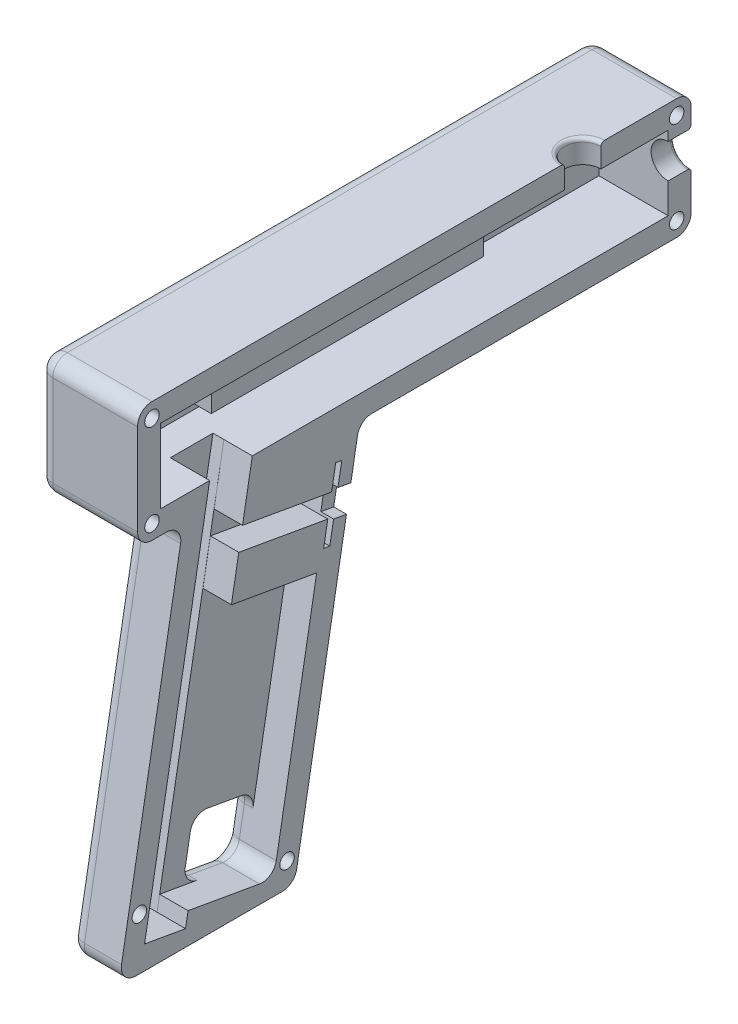
SolidWorks part; units mm, degrees
ref_plane "Front Plane" through (0, 0, 0) normal (0, 0, 1) x (1, 0, 0)
ref_plane "Top Plane" through (0, 0, 0) normal (0, 1, 0) x (1, 0, 0)
ref_plane "Right Plane" through (0, 0, 0) normal (1, 0, 0) x (0, 0, -1)
sketch "Sketch1" plane through (0, 0, 0) normal (0, 0, 1) x (1, 0, 0)
  line L1 (0, 0) -> (27.305, 0)
  line L2 (0, 0) -> (0, 33.1)
  line L3 (0, 33.1) -> (27.305, 33.1)
  line L4 (27.305, 0) -> (27.305, 33.1)
  dimension "D1" = 33.1
  dimension "D2" = 27.305
extrude "Boss-Extrude1" add sketch "Sketch1" against normal blind 152.4
sketch "Sketch2" plane through (27.305, 0, 0) normal (1, 0, 0) x (0, 0, -1)
  line L0 (0, 0) -> (0, 33.1) construction
  line L1 (6.35, 26.75) -> (146.05, 26.75)
  line L2 (6.35, 26.75) -> (6.35, 6.35)
  line L3 (6.35, 6.35) -> (146.05, 6.35)
  line L4 (146.05, 26.75) -> (146.05, 6.35)
  line L5 (152.4, 33.1) -> (0, 33.1) construction
  line L6 (152.4, 0) -> (0, 0) construction
  line L7 (152.4, 0) -> (152.4, 33.1) construction
  point P12 (6.35, 16.55)
  point P13 (0, 16.55)
  dimension "D1" = 6.35
  dimension "D2" = 6.35
  dimension "D3" = 6.35
  dimension "D4" = 6.35
extrude "Cut-Extrude1" cut sketch "Sketch2" against normal blind 19.05
sketch "Sketch4" plane through (0, 33.1, 0) normal (0, 1, 0) x (1, 0, 0)
  line L0 (27.305, 152.4) -> (27.305, 0) construction
  line L2 (27.305, 117.555) -> (27.305, 127.555)
  line L3 (27.305, 152.4) -> (0, 152.4) construction
  arc A2 (27.305, 117.555) -> (27.305, 127.555) centre (27.305, 122.555) cw
  dimension "D1" = 29.845
sketch "Sketch5" plane through (8.255, 0, 0) normal (1, 0, 0) x (0, 0, -1)
  line L0 (33.02, 17.4) -> (107.95, 17.4)
  line L1 (33.02, 23.75) -> (107.95, 23.75)
  line L2 (33.02, 23.75) -> (33.02, 9.35)
  line L3 (33.02, 9.35) -> (107.95, 9.35)
  line L4 (107.95, 23.75) -> (107.95, 9.35)
  line L9 (33.02, 15.7) -> (107.95, 15.7)
  line L10 (6.35, 6.35) -> (146.05, 6.35) construction
  line L11 (146.05, 6.35) -> (146.05, 26.75) construction
  line M13 (146.05, 6.35) -> (146.05, 26.75)
  dimension "D1" = 1.7
  dimension "D2" = 6.35
  dimension "D3" = 6.35
  dimension "D4" = 3
  dimension "D5" = 38.1
  dimension "D6" = 74.93
extrude "PCB Slot" add sketch "Sketch5" along normal blind 6.35 contours L1 L2 L0 M13 | L9 L2 L3 M13 region at (8.255, 20.575, -70.485) region at (8.255, 12.525, -70.485)
sketch "Sketch8" plane through (27.305, 0, 25.4) normal (1, 0, 0) x (0, 0, -1)
  line L0 (38.1, 0) -> (20.1852, -101.6)
  line L1 (20.1852, -101.6) -> (68.621, -101.6)
  line L2 (68.621, -101.6) -> (86.5358, 0)
  line L4 (38.1, 0) -> (86.5358, 0)
  dimension "D1" = 12.7
  dimension "D3" = 47.7
extrude "Butt" add sketch "Sketch8" against normal blind 14.175
sketch "Sketch9" plane through (27.305, 0, 25.4) normal (1, 0, 0) x (0, 0, -1)
  line L7 (68.621, -101.6) -> (86.5358, 0) construction
  line L8 (51.2564, -26.2652) -> (74.7269, -30.4036)
  line L9 (28.0575, -91.2236) -> (62.9188, -97.3706)
  line L10 (74.7269, -30.4036) -> (62.9188, -97.3706)
  line L12 (31.75, 6.35) -> (171.45, 6.35) construction
  line L13 (45.2623, 6.35) -> (57.0073, 6.35)
  line L14 (57.0073, 6.35) -> (51.2564, -26.2652)
  line L15 (45.2623, 6.35) -> (28.0575, -91.2236)
  dimension "D3" = 68
  dimension "D4" = 3.175
extrude "BatteryPack" cut sketch "Sketch9" against normal blind 7.825
sketch "Sketch10" plane through (19.48, 0, 0) normal (1, 0, 0) x (0, 0, -1)
  line L0 (37.5188, -97.3706) -> (20.2847, -94.3317)
  line L1 (37.5188, -97.3706) -> (40.2972, -81.6136)
  line L2 (20.2847, -94.3317) -> (23.0631, -78.5748)
  line L3 (40.2972, -81.6136) -> (23.0631, -78.5748)
  line L4 (2.6575, -91.2236) -> (37.5188, -97.3706) construction
  dimension "D1" = 16
  dimension "D2" = 17.5
extrude "BatterySwitch" cut sketch "Sketch10" against normal up to next
sketch "Sketch11" plane through (0, -88.0184, 15.52) normal (0, 0.9848, -0.1736) x (1, 0, 0)
  line L0 (19.48, 18.4579) -> (27.305, 18.4579)
  line L1 (19.48, 18.4579) -> (19.48, 29.8992)
  line L2 (27.305, 18.4579) -> (27.305, 29.8992)
  line L3 (19.48, 29.8992) -> (27.305, 29.8992)
  dimension "D1" = 11.4413
extrude "WireSpace" cut sketch "Sketch11" against normal blind 4
sketch "Sketch12" plane through (19.48, 0, 0) normal (1, 0, 0) x (0, 0, -1)
  line L0 (19.8623, 6.35) -> (31.6073, 6.35)
  line L1 (31.6073, 6.35) -> (13.2303, -97.1496)
  line L2 (13.2303, -97.1496) -> (1.9629, -95.1628)
  line L3 (1.9629, -95.1628) -> (19.8623, 6.35)
extrude "WireRoute" cut sketch "Sketch12" against normal blind 3
fillet "Fillet-Body" radius 4 24 edges at (13.6525, 0, -152.4) (20.2175, 0, -61.1358) (16.305, -78.5748, -23.0631) (16.305, -94.3317, -20.2847) (13.13, -89.4921, -38.908) (13.13, -95.8511, -28.9018) (13.13, -80.0942, -31.6801) (13.13, -86.4533, -21.6739) (20.2175, -97.3706, -37.5188) (16.305, -81.6136, -40.2972) (20.2175, -101.6, -43.221) (13.13, -101.6, -19.0031) (20.2175, -101.6, 5.2148) (0, 16.55, -152.4) (0, 0, -76.2) (13.13, -50.8, -52.1784) (13.13, -50.8, -3.7426) (13.13, 0, -36.9179) (20.2175, 0, -12.7) (13.6525, 0, 0) (0, 16.55, 0) (13.6525, 33.1, -152.4) (0, 33.1, -76.2) (13.6525, 33.1, 0)
sketch "Sketch13" plane through (27.305, 0, 0) normal (1, 0, 0) x (0, 0, -1)
  line L0 (148.4, 33.1) -> (4, 33.1) construction
  line L1 (0, 4) -> (0, 29.1) construction
  line L2 (7.933, 0) -> (4, 0) construction
  line L3 (152.4, 4) -> (152.4, 29.1) construction
  line L8 (49.3269, -30.4036) -> (25.8564, -26.2652) construction
  line L9 (43.8039, -98.2946) -> (60.553, -3.3054) construction
  line L10 (11.8722, -4.6946) -> (-4.387, -96.9054) construction
  circle A0 centre (4, 29.1) radius 2
  circle A1 centre (148.4, 29.1) radius 2
  circle A2 centre (148.4, 4) radius 2
  circle A3 centre (4, 4) radius 2
  circle A5 centre (0.5231, -87.3425) radius 2
  circle A6 centre (41.1665, -94.9675) radius 2
  dimension "D1" = 4
  dimension "D5" = 64.5486
  dimension "D2" = 4
  dimension "D3" = 4
  dimension "D4" = 4
  dimension "D6" = 65
  dimension "D7" = 3.175
  dimension "D8" = 3.175
extrude "PressFit" cut sketch "Sketch13" against normal blind 5
extrude "HitLED" cut sketch "Sketch4" against normal up to next
sketch "Sketch15" plane through (0, 0, -146.05) normal (0, 0, 1) x (1, 0, 0)
  line L0 (27.305, 6.35) -> (27.305, 26.75) construction
  line L1 (27.305, 24.05) -> (27.305, 14.65)
  arc A0 (27.305, 14.65) -> (27.305, 24.05) centre (27.305, 19.35) cw
  dimension "D1" = 13
extrude "IRLED" cut sketch "Sketch15" against normal up to next
fillet "Fillet-LED's" radius 1 2 edges at (22.605, 19.35, -152.4) (22.305, 33.1, -122.555)
sketch "Sketch16" plane through (27.305, 0, 0) normal (1, 0, 0) x (0, 0, -1)
  line L0 (55.1893, -12.9928) -> (53.9738, -19.8865)
  line L1 (53.9738, -19.8865) -> (57.5191, -20.5116)
  line L2 (57.5191, -20.5116) -> (58.7346, -13.618)
  line L3 (58.7346, -13.618) -> (55.1893, -12.9928)
  line L4 (43.8039, -98.2946) -> (60.553, -3.3054) construction
  line L5 (49.3269, -30.4036) -> (25.8564, -26.2652) construction
  point P9 (56.962, -13.3054)
  dimension "D1" = 7
  dimension "D2" = 3.6
  dimension "D3" = 0
  dimension "D4" = 10
extrude "Trigger" cut sketch "Sketch16" against normal blind 3.5
sketch "Sketch18" plane through (27.305, 0, 0) normal (1, 0, 0) x (0, 0, -1)
  line L0 (54.5614, -6.7642) -> (51.2534, -25.5248)
  line L1 (51.2534, -25.5248) -> (52.9276, -25.82)
  line L2 (52.9276, -25.82) -> (56.2356, -7.0594)
  line L3 (56.2356, -7.0594) -> (54.5614, -6.7642)
  line L4 (55.1893, -12.9928) -> (53.9738, -19.8865) construction
  line L5 (58.7346, -13.618) -> (55.1893, -12.9928) construction
  point P6 (55.3985, -6.9118)
  dimension "D1" = 0
  dimension "D2" = 1.7
  dimension "D3" = 19.05
  dimension "D4" = 6.025
extrude "ButtonPCB" cut sketch "Sketch18" against normal blind 12.065 contours L3 L0 L1 L2
sketch "Sketch20" plane through (27.305, 0, 0) normal (1, 0, 0) x (0, 0, -1)
  line L0 (28.9237, -8.8692) -> (53.4283, -13.19)
  line L1 (25.8564, -26.2652) -> (31.6073, 6.35) construction
  line L2 (54.5614, -6.7642) -> (51.2534, -25.5248) construction
  line L3 (53.4283, -13.19) -> (52.3864, -19.0989)
  line L4 (52.3864, -19.0989) -> (27.8818, -14.7781)
  line L5 (27.8818, -14.7781) -> (28.9237, -8.8692)
  line L6 (51.2534, -25.5248) -> (52.9276, -25.82) construction
  line L7 (56.2356, -7.0594) -> (54.5614, -6.7642) construction
  dimension "D1" = 6
  dimension "D2" = 6.525
extrude "ButtonWireSpace" cut sketch "Sketch20" against normal up to vertex (7.825 mm away) up to point (19.48, 6.35, -31.6073)
